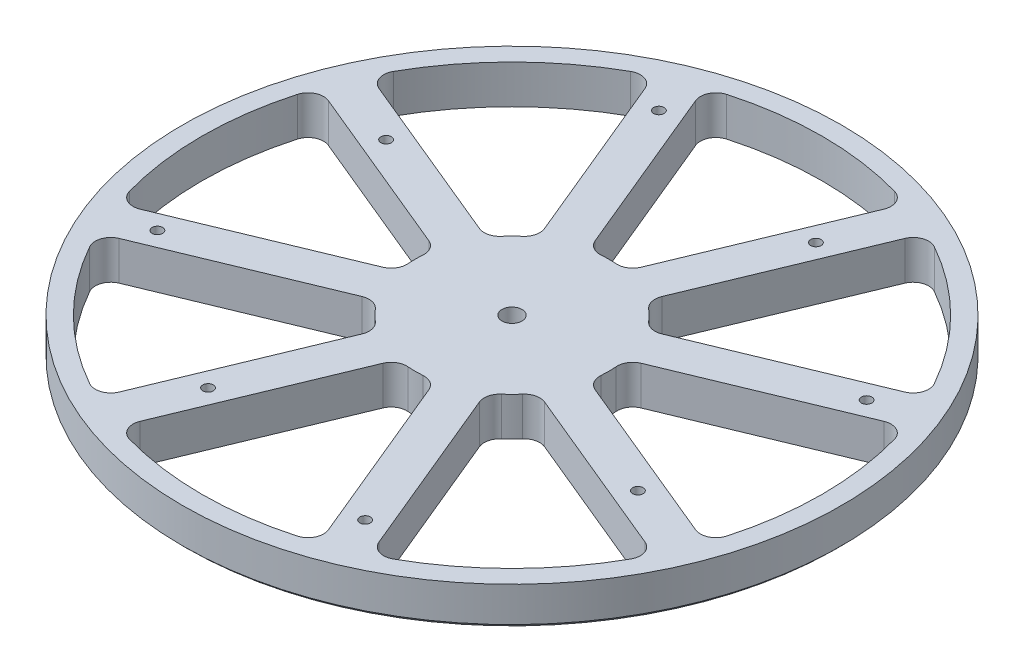
SolidWorks part; units mm, degrees
ref_plane "Front Plane" through (0, 0, 0) normal (0, 0, 1) x (1, 0, 0)
ref_plane "Top Plane" through (0, 0, 0) normal (0, 1, 0) x (1, 0, 0)
ref_plane "Right Plane" through (0, 0, 0) normal (1, 0, 0) x (0, 0, -1)
sketch "Sketch2" plane through (0, 0, 0) normal (1, 0, 0) x (0, 0, -1)
  line L0 (0, 0) -> (-84.9998, 0)
  line L1 (-84.9998, 0) -> (-84.9998, 10)
  line L2 (-84.9998, 10) -> (0, 10)
  line L5 (0, 10) -> (0, 0)
  dimension "D1" = 84.9998
  dimension "D2" = 10
ref_axis "Axis1" through (0, -0.75, 0) along (0, 1, 0)
revolve "Revolve1" add sketch "Sketch2" angle 360 about axis through (0, -0.75, 0) along (0, 1, 0)
hole_wizard "#6-32 Tapped Hole1" positions "Sketch6" profile "Sketch7" tap size "#6-32" standard "ANSI Inch" end condition through all
sketch "Sketch6" plane through (0, 10, 0) normal (0, 1, 0) x (1, 0, 0)
  line L0 (0, 0) -> (-53.438, 129.0108) construction
  line L2 (0, 0) -> (0, 109.0908) construction
  line L3 (0, 0) -> (-78.5296, 32.528) construction
  circle A0 centre (0, 0) radius 84.9998 construction
  point P0 (-26.7878, 64.6716)
  point P18 (-55.4328, 22.961)
  dimension "D1" = 22.5
  dimension "D2" = 70
  dimension "D3" = 45
  dimension "D4" = 60
sketch "Sketch7" plane through (-26.7878, 10, -64.6716) normal (1, 0, 0) x (0, 0, 1)
  line L0 (0, 0) -> (0, 10)
  line L1 (0, 10) -> (1.3525, 10)
  line L2 (1.3525, 10) -> (1.3525, 0)
  line L5 (1.3525, 0) -> (0, 0)
  line L11 (0, -6.35) -> (0, 107.95) construction
  dimension "Thread Major Dia." = 2.7051
  dimension "Thru Tap Drill Depth" = 10
pattern_circular "CirPattern3" count 4 over 360 about axis through (0, -0.75, 0) along (0, 1, 0) of "#6-32 Tapped Hole1"
sketch "Sketch8" plane through (0, 10, 0) normal (0, 1, 0) x (1, 0, 0)
  line L4 (0, 0) -> (0, 93.9995) construction
  line L5 (0, 0) -> (113.8372, 0) construction
  line L6 (-4.7544, 24.5438) -> (-25.9354, 75.6791)
  line L7 (4.7544, 24.5438) -> (25.9354, 75.6791)
  line L8 (0, 0) -> (-26.7878, 64.6716) construction
  arc A0 (-4.7544, 24.5438) -> (4.7544, 24.5438) centre (0, 0) cw
  arc A1 (-25.9354, 75.6791) -> (25.9354, 75.6791) centre (0, 0) cw
  circle A2 centre (0, 0) radius 84.9998 construction
  dimension "D1" = 25
  dimension "D2" = 5
  dimension "D3" = 5
extrude "Cut-Extrude1" cut sketch "Sketch8" against normal through all
fillet "Fillet1" radius 4 4 edges at (4.7544, 5, -24.5438) (25.9354, 5, -75.6791) (-4.7544, 5, -24.5438) (-25.9354, 5, -75.6791)
pattern_circular "CirPattern4" count 8 over 360 about axis through (0, -0.75, 0) along (0, 1, 0) of "Cut-Extrude1", "Fillet1"
chamfer "Chamfer2" distance 1 angle 45 1 edges at (0, 0, -84.9998)
hole_wizard "#6 (0.204) Diameter Hole2" positions "Sketch9" profile "Sketch11" hole size "#6" standard "ANSI Inch" end condition through all
sketch "Sketch9" plane through (0, 0, 0) normal (0, -1, 0) x (-1, 0, 0)
  point P0 (0, 0)
sketch "Sketch11" plane through (0, 0, 0) normal (1, 0, 0) x (0, 0, -1)
  line L0 (0, 0) -> (0, 10)
  line L1 (0, 10) -> (2.5908, 10)
  line L2 (2.5908, 10) -> (2.5908, 0)
  line L5 (2.5908, 0) -> (0, 0)
  line L11 (0, -6.35) -> (0, 107.95) construction
  dimension "Thru Hole Dia." = 5.1816
  dimension "Thru Hole Depth" = 10
